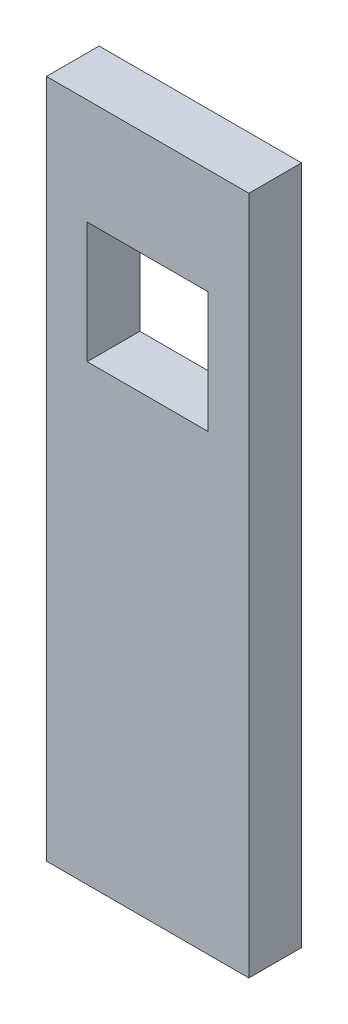
SolidWorks part; units mm, degrees
ref_plane "Front Plane" through (0, 0, 0) normal (0, 0, 1) x (1, 0, 0)
ref_plane "Top Plane" through (0, 0, 0) normal (0, 1, 0) x (1, 0, 0)
ref_plane "Right Plane" through (0, 0, 0) normal (1, 0, 0) x (0, 0, -1)
sketch "Sketch1" plane through (0, 0, 0) normal (0, 0, 1) x (1, 0, 0)
  line L0 (0, 67.15) -> (0, 44.75)
  line L1 (0, 67.15) -> (20, 67.15)
  line L2 (0, 44.75) -> (0, 39.55)
  line L3 (20, 0) -> (0, 0)
  line L4 (4.025, 56.7) -> (15.975, 56.7)
  line L5 (4.025, 44.75) -> (15.975, 44.75)
  line L6 (4.025, 56.7) -> (4.025, 44.75)
  line L7 (15.975, 56.7) -> (15.975, 44.75)
  line L8 (0, 44.75) -> (20, 44.75) construction
  line L9 (0, 39.55) -> (20, 39.55) construction
  line L10 (0, 39.55) -> (0, 27.6)
  line L11 (0, 27.6) -> (0, 22.4)
  line L12 (20, 44.75) -> (20, 39.55)
  line L13 (20, 67.15) -> (20, 44.75)
  line L14 (0, 22.4) -> (0, 0)
  line L15 (20, 39.55) -> (20, 27.6)
  line L16 (20, 27.6) -> (20, 22.4)
  line L17 (20, 22.4) -> (20, 0)
  line L18 (0, 27.6) -> (20, 27.6) construction
  line L19 (20, 22.4) -> (0, 22.4) construction
  line L20 (10, -0.0005) -> (10, 4.0956) construction
  point P18 (10, 44.75)
  point P20 (10, 56.7)
  point P21 (10, 67.15)
  dimension "D1" = 22.4
  dimension "D2" = 11.95
  dimension "D3" = 5.2
  dimension "D4" = 20
  dimension "D5" = 11.95
  dimension "D6" = 11.95
extrude "Boss-Extrude1" add sketch "Sketch1" along normal mid plane 5.2
